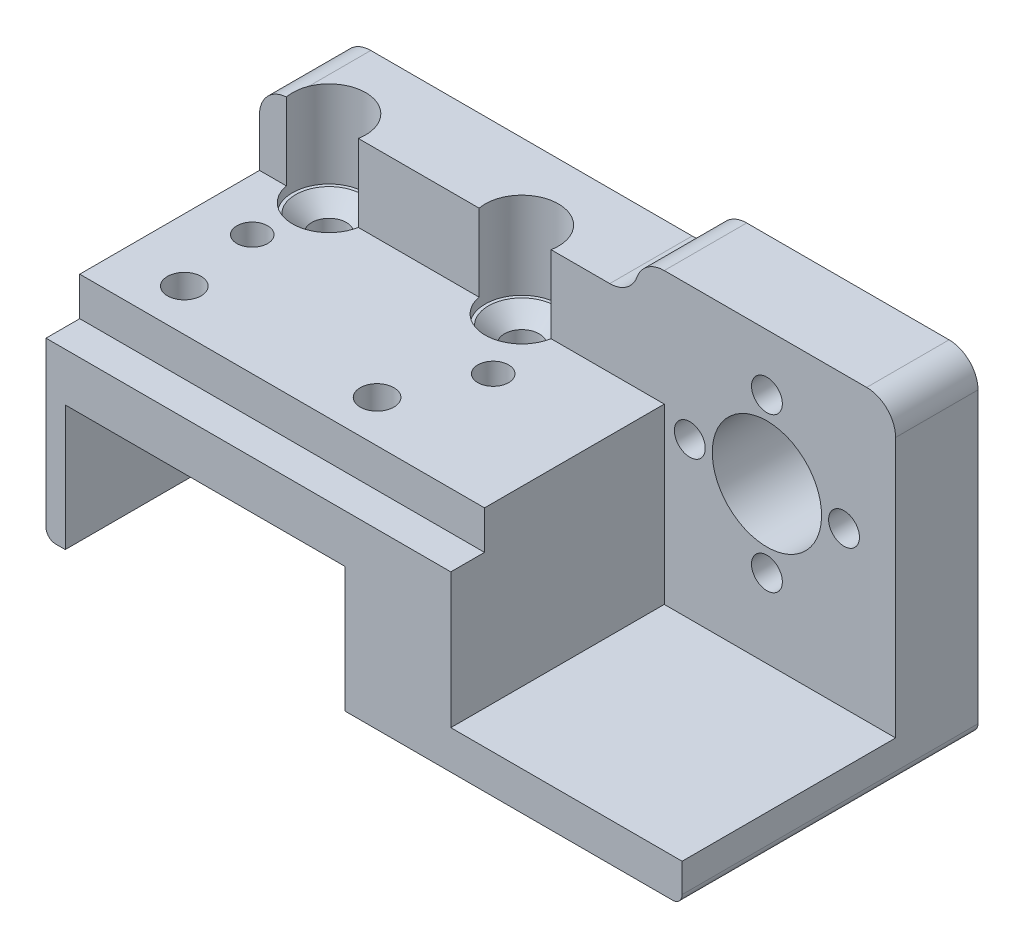
SolidWorks part; units mm, degrees
ref_plane "Front Plane" through (0, 0, 0) normal (0, 0, 1) x (1, 0, 0)
ref_plane "Top Plane" through (0, 0, 0) normal (0, 1, 0) x (1, 0, 0)
ref_plane "Right Plane" through (0, 0, 0) normal (1, 0, 0) x (0, 0, -1)
sketch "Croquis2" plane through (0, 0, 0) normal (0, 0, 1) x (1, 0, 0)
  line L0 (-42.15, -17.65) -> (-49.65, -17.65) construction
  line L1 (-42.15, -17.65) -> (-49.65, -17.65) construction
  line L2 (-49.65, -7.65) -> (-49.65, -17.65) construction
  line L3 (-49.65, -7.65) -> (-49.65, -17.65) construction
  line L5 (-52.65, -20.15) -> (13.35, -20.15)
  line L6 (-52.65, -20.15) -> (-52.65, 13.85)
  line L7 (-52.65, 13.85) -> (13.35, 13.85)
  line L8 (13.35, -20.15) -> (13.35, 13.85)
  line L9 (-50.65, -7.65) -> (-50.65, -7.15)
  line L10 (-21.65, -7.65) -> (-21.65, -17.65)
  line L11 (-21.65, -7.65) -> (-21.65, -20.15)
  line L13 (-50.65, -7.15) -> (-49.65, -7.15)
  line L14 (-21.65, -7.65) -> (-21.65, -7.15)
  line L15 (-21.65, -7.15) -> (-22.65, -7.15)
  line L16 (-50.65, -20.15) -> (-21.65, -20.15)
  line L17 (-30.45, -21.15) -> (-41.85, -21.15) construction
  line L18 (-49.65, -7.15) -> (-22.65, -7.15)
  line L19 (-49.65, -7.15) -> (-22.65, -7.15)
  line L28 (-50.65, -7.65) -> (-50.65, -17.65)
  line L29 (-50.65, -7.65) -> (-50.65, -20.15)
  circle A2 centre (0, 0) radius 5.67
  circle A3 centre (0, 0) radius 5.67
  circle A5 centre (0, 8) radius 1.3
  circle A6 centre (0, 8) radius 1.3
  circle A8 centre (8, 0) radius 1.3
  circle A9 centre (8, 0) radius 1.3
  circle A11 centre (0, -8) radius 1.3
  circle A12 centre (0, -8) radius 1.3
  circle A14 centre (-8, 0) radius 1.3
  circle A15 centre (-8, 0) radius 1.3
  circle M7 centre (0, 8) radius 1.6
  circle M8 centre (0, -8) radius 1.6
  circle M9 centre (8, 0) radius 1.6
  circle M10 centre (-8, 0) radius 1.6
  circle M12 centre (0, 0) radius 10.875
  dimension "D6" = 3
  dimension "D7" = 66
  dimension "D8" = 34
  dimension "D12" = 1
  dimension "D1" = 0.5
  dimension "D2" = 0.3
  dimension "D3" = 0.3
  dimension "D4" = 0.3
  dimension "D5" = 0.3
  dimension "D9" = 0.5
  dimension "D10" = 1
  dimension "D11" = 1
extrude "Saliente-Extruir1" add sketch "Croquis2" along normal offset from surface (30.7 mm away) 2 contours L29 L9 L13 L19 L15 L14 L11 L5 L8 L7 L6 M12 | A3 M12 M8 M10 M9 M7 region at (-20.3724, -1.2856, 0) region at (-10.5674, 0, 0)
sketch "Croquis4" plane through (0, 0, 30.7) normal (0, 0, 1) x (1, 0, 0)
  line L0 (-52.65, 13.85) -> (13.35, 13.85) construction
  line L1 (-10.65, 13.85) -> (13.35, 13.85)
  line L2 (-10.65, 13.85) -> (-10.65, -16.15)
  line L3 (-10.65, -16.15) -> (13.35, -16.15)
  line L4 (13.35, 13.85) -> (13.35, -16.15)
  line L5 (13.35, -20.15) -> (13.35, 13.85) construction
  line M9 (13.35, -20.15) -> (13.35, 13.85)
  line M10 (13.35, 13.85) -> (-52.65, 13.85)
  circle M13 centre (0, 0) radius 5.67
  circle M14 centre (0, -8) radius 1.6
  circle M15 centre (-8, 0) radius 1.6
  circle M16 centre (8, 0) radius 1.6
  circle M17 centre (0, 8) radius 1.6
  dimension "D1" = 24
  dimension "D2" = 30
extrude "Cortar-Extruir2" cut sketch "Croquis4" against normal offset from surface (22.7 mm away) 8 contours L2 L3 M9 M10 M13 M15 M17 M16 M14 region at (1.35, 13.4658, 30.7) up to face at (-27.9, -8.4, 0)
sketch "Croquis6" plane through (0, 0, 30.7) normal (0, 0, 1) x (1, 0, 0)
  line L0 (-30.15, -17.65) -> (-30.15, -13.15) construction
  line L1 (-21.65, -20.15) -> (-50.65, -20.15)
  line L2 (-21.65, -20.15) -> (-21.65, -7.15)
  line L3 (-21.65, -7.15) -> (-50.65, -7.15)
  line L4 (-50.65, -20.15) -> (-50.65, -7.15)
  line L5 (-30.15, -13.15) -> (-42.15, -13.15) construction
  line L6 (-42.15, -13.15) -> (-42.15, -17.65) construction
  line L7 (-29.65, -20.15) -> (-29.65, -12.65)
  line L8 (-29.65, -12.65) -> (-42.65, -12.65)
  line L9 (-42.65, -12.65) -> (-42.65, -20.15)
  line L10 (-29.65, -17.65) -> (-29.65, -12.65) construction
  line L11 (-42.65, -12.65) -> (-42.65, -17.65) construction
  dimension "D1" = 0.5
sketch "Croquis3" plane through (-52.65, 0, 0) normal (-1, 0, 0) x (0, 0, 1)
  line L0 (-2, -7.65) -> (32.7, -7.65) construction
  line L1 (20.85, 1.85) -> (8.55, 1.85)
  line L2 (20.85, 1.85) -> (20.85, 9.85)
  line L3 (20.85, 9.85) -> (8.55, 9.85)
  line L4 (8.55, 1.85) -> (8.55, 9.85)
  line L5 (0, -20.15) -> (0, 13.85) construction
  line L6 (30.7, 13.85) -> (30.7, -20.15) construction
  dimension "D1" = 8
  dimension "D2" = 12.3
  dimension "D3" = 9.5
  dimension "D4" = 9.85
  dimension "D5" = 8.55
extrude "Cortar-Extruir5" cut sketch "Croquis3" against normal blind 42
sketch "Croquis5" plane through (0, 13.85, 0) normal (0, 1, 0) x (1, 0, 0)
  line L0 (-10.65, -20.85) -> (-10.65, -8.55) construction
  line L1 (-52.65, -20.85) -> (-52.65, -8.55) construction
  line L2 (-52.65, -14.7) -> (-11.635, -14.7) construction
  line L5 (-52.65, -20.85) -> (-52.65, -8.55)
  circle A0 centre (-47.25, -14.7) radius 1.6
  circle A1 centre (-22.25, -14.7) radius 1.6
  point P15 (-52.65, -14.7)
  dimension "D3" = 3.2
  dimension "D1" = 11.6
  dimension "D2" = 25
extrude "Cortar-Extruir6" cut sketch "Croquis5" against normal through all contours L2 A0 | A0 L2 | A1 L2 | L2 A1 region at (-47.25, 13.85, 14.0209) region at (-22.25, 13.85, 14.0209) region at (-22.25, 13.85, 15.3791) region at (-47.25, 13.85, 15.3791)
sketch "Croquis7" plane through (0, 13.85, 0) normal (0, 1, 0) x (1, 0, 0)
  line L0 (-52.65, 0) -> (13.35, 0) construction
  line L1 (-52.65, -30.7) -> (-10.65, -30.7)
  line L2 (-52.65, -30.7) -> (-52.65, 0)
  line L3 (-52.65, 0) -> (-10.65, 0)
  line L4 (-10.65, -30.7) -> (-10.65, 0)
  line L5 (-52.65, -8.55) -> (-52.65, -20.85) construction
  line L6 (-52.65, -8.55) -> (-52.65, -20.85)
  line L8 (-52.65, -20.85) -> (-10.65, -20.85)
  line L9 (-52.65, -20.85) -> (-52.65, -30.7)
  line L10 (-52.65, -30.7) -> (-10.65, -30.7)
  line L11 (-10.65, -20.85) -> (-10.65, -30.7)
  line M3 (-10.65, -30.7) -> (-10.65, -8)
  line M6 (13.35, 0) -> (-52.65, 0)
  line M7 (-52.65, 0) -> (-52.65, -30.7)
  line M8 (-52.65, -30.7) -> (-10.65, -30.7)
  circle M15 centre (-47.25, -14.7) radius 1.6
  circle M16 centre (-22.25, -14.7) radius 1.6
extrude "Cortar-Extruir7" cut sketch "Croquis7" against normal up to surface (4 mm away) contours L2 L8 L4 M6 M7 M16 M15 region at (-31.592, 13.85, 10.345) up to face at (-47.25, 9.85, 16.3)
sketch "Croquis9" plane through (-10.65, 0, 0) normal (-1, 0, 0) x (0, 0, 1)
  line L4 (8, 9.85) -> (8, 13.85)
  line L5 (8, 13.85) -> (0, 13.85)
  line L6 (0, 13.85) -> (0, 9.85)
  line L7 (0, 9.85) -> (8, 9.85)
  line L8 (8, 9.85) -> (8, 13.85)
  line L9 (8, 13.85) -> (0, 13.85)
  line L10 (0, 13.85) -> (0, 9.85)
  line L11 (0, 9.85) -> (8, 9.85)
  dimension "D1" = 0
extrude "Saliente-Extruir4" add sketch "Croquis9" along normal blind 3
extrude "Cortar-Extruir8" cut sketch "Croquis7<3>" against normal up to surface (12 mm away) contours L8 M7 M8 M3 region at (-31.65, 13.85, 25.775) up to face at (-47.25, 1.85, 13.1)
sketch "Croquis7<3>" plane through (0, 13.85, 0) normal (0, 1, 0) x (1, 0, 0) same geometry as "Croquis7"
sketch "Croquis11" plane through (0, 1.85, 0) normal (0, 1, 0) x (1, 0, 0)
  line L1 (-47.25, -10.3121) -> (-51.05, -12.5061)
  line L2 (-51.05, -12.5061) -> (-51.05, -16.8939)
  line L3 (-51.05, -16.8939) -> (-47.25, -19.0879)
  line L4 (-47.25, -19.0879) -> (-43.45, -16.8939)
  line L5 (-43.45, -16.8939) -> (-43.45, -12.5061)
  line L6 (-43.45, -12.5061) -> (-47.25, -10.3121)
  line L7 (-22.25, -10.3121) -> (-26.05, -12.5061)
  line L8 (-26.05, -12.5061) -> (-26.05, -16.8939)
  line L9 (-26.05, -16.8939) -> (-22.25, -19.0879)
  line L10 (-22.25, -19.0879) -> (-18.45, -16.8939)
  line L11 (-18.45, -16.8939) -> (-18.45, -12.5061)
  line L12 (-18.45, -12.5061) -> (-22.25, -10.3121)
  circle A0 centre (-46.1299, -7.85) radius 1.5 construction
  circle A1 centre (-26.1299, -7.85) radius 1.5 construction
  circle A2 centre (-26.15, -22.85) radius 1.5 construction
  circle A3 centre (-46.15, -22.85) radius 1.5 construction
  circle A4 centre (-46.1299, -7.85) radius 1.5 construction
  circle A5 centre (-26.1299, -7.85) radius 1.5 construction
  circle A6 centre (-26.15, -22.85) radius 1.5 construction
  circle A7 centre (-46.15, -22.85) radius 1.5 construction
  circle A8 centre (-46.1299, -7.85) radius 3.8
  circle A9 centre (-26.1299, -7.85) radius 3.8
  circle A10 centre (-26.15, -22.85) radius 3.8
  circle A11 centre (-46.15, -22.85) radius 3.8
  circle A12 centre (-47.25, -14.7) radius 3.8 construction
  circle A13 centre (-22.25, -14.7) radius 3.8 construction
  circle A14 centre (-46.1299, -7.85) radius 1.75
  circle A15 centre (-26.1299, -7.85) radius 1.75
  circle A16 centre (-26.15, -22.85) radius 1.75
  circle A17 centre (-46.15, -22.85) radius 1.75
  circle M13 centre (-47.25, -14.7) radius 1.6
  circle M14 centre (-22.25, -14.7) radius 1.6
  line M18 (-10.65, -8.55) -> (-52.65, -8.55)
  dimension "D1" = 7.6
  dimension "D2" = 7.6
  dimension "D3" = 3.5
extrude "Cortar-Extruir9" cut sketch "Croquis11" against normal offset from surface (9 mm away) 1 from surface contours A14 A8 M18 | A14 A8 L1 L6 M18 | L1 A8 L6 | A14 M18 | A14 M18 | A15 A9 M18 | A15 M18 | A15 M18 | A15 A9 M18 region at (-46.8614, 1.85, 11.0938) region at (-46.0098, 1.85, 9.8058) region at (-26.4732, 1.85, 4.1542) region at (-26.1299, 1.85, 9.9873) region at (-46.4732, 1.85, 4.1542) region at (-46.1299, 1.85, 8.9831) region at (-46.1299, 1.85, 7.4676) region at (-26.1299, 1.85, 8.9831) region at (-26.1299, 1.85, 7.4676) up to face at (-47.25, 1.85, 13.1) offset beyond the face yes starting at face at (-25.65, 9.85, 5.5167)
extrude "Cortar-Extruir10" cut sketch "Croquis11<3>" against normal through all contours A14 M18 | A14 M18 | A15 M18 | A15 M18 | A16 | A17 region at (-46.1299, 1.85, 8.9831) region at (-46.1299, 1.85, 7.4676) region at (-26.1299, 1.85, 8.9831) region at (-26.1299, 1.85, 7.4676) region at (-26.15, 1.85, 22.85) region at (-46.15, 1.85, 22.85)
sketch "Croquis11<3>" plane through (0, 1.85, 0) normal (0, 1, 0) x (1, 0, 0) same geometry as "Croquis11"
extrude "Cortar-Extruir11" cut sketch "Croquis11<4>" along normal blind 4 and the other way through all from surface contours A8 L1 L2 L3 L4 L5 L6 M13 | L11 L12 L7 L8 L9 L10 M14 | L1 A8 L6 region at (-46.8614, 1.85, 11.0938) region at (-46.8317, 1.85, 11.6979) region at (-20.408, 1.85, 11.5096) starting at face at (-46.15, -7.15, 24.6)
sketch "Croquis11<4>" plane through (0, 1.85, 0) normal (0, 1, 0) x (1, 0, 0) same geometry as "Croquis11"
hole_wizard "Avellanado para tornillo con cabeza avellanada de clavija hexagonal de M31" positions "Croquis16" profile "Croquis17" countersink size "M3" standard "DIN" end condition through all
sketch "Croquis16" plane through (0, 0.85, 0) normal (0, 1, 0) x (1, 0, 0)
  point P0 (-46.1299, -7.85)
  point P3 (-26.1299, -7.85)
sketch "Croquis17" plane through (-46.1299, 0.85, 7.85) normal (1, 0, 0) x (0, 0, 1)
  line L0 (0, 0) -> (0, 21)
  line L1 (0, 21) -> (1.8, 21)
  line L2 (1.8, 21) -> (1.8, 1.67)
  line L3 (1.8, 1.67) -> (3.47, 0)
  line L5 (3.47, 0) -> (0, 0)
  line L6 (-1.8, 1.67) -> (-3.47, 0) construction
  line L11 (0, -6.35) -> (0, 107.95) construction
  dimension "Diámetro de taladro hasta el siguiente" = 3.6
  dimension "Profundidad de taladro hasta el siguiente" = 21
  dimension "Diámetro de avellanado cercano" = 6.94
  dimension "Ángulo de avellanado cercano" = 90
sketch "Croquis18" plane through (0, 1.85, 0) normal (0, 1, 0) x (1, 0, 0)
  line L0 (-10.65, -8.55) -> (-10.65, -30.7) construction
  line L1 (-52.65, -30.7) -> (-10.65, -30.7)
  line L2 (-52.65, -30.7) -> (-52.65, -27.2)
  line L3 (-52.65, -27.2) -> (-10.65, -27.2)
  line L4 (-10.65, -30.7) -> (-10.65, -27.2)
  dimension "D1" = 3.5
extrude "Cortar-Extruir12" cut sketch "Croquis18" against normal blind 4
sketch "Croquis19" plane through (0, 0, 8) normal (0, 0, 1) x (1, 0, 0)
  line L6 (-10.65, 9.85) -> (-10.65, -16.15)
  line L7 (-10.65, -16.15) -> (13.35, -16.15)
  line L8 (13.35, -16.15) -> (13.35, 13.85)
  line L9 (13.35, 13.85) -> (-13.65, 13.85)
  line L10 (-13.65, 13.85) -> (-13.65, 9.85)
  line L11 (-13.65, 9.85) -> (-10.65, 9.85)
  line L12 (-10.65, 9.85) -> (-10.65, -16.15)
  line L13 (-10.65, -16.15) -> (13.35, -16.15)
  line L14 (13.35, -16.15) -> (13.35, 13.85)
  line L15 (13.35, 13.85) -> (-13.65, 13.85)
  line L16 (-13.65, 13.85) -> (-13.65, 9.85)
  line L17 (-13.65, 9.85) -> (-10.65, 9.85)
  circle A0 centre (0, 0) radius 5.67 construction
  circle A1 centre (0, -8) radius 1.6 construction
  circle A2 centre (8, 0) radius 1.6 construction
  circle A3 centre (0, 8) radius 1.6 construction
  circle A4 centre (-8, 0) radius 1.6 construction
  circle A5 centre (0, 0) radius 5.67
  circle A6 centre (0, -8) radius 1.6
  circle A7 centre (8, 0) radius 1.6
  circle A8 centre (0, 8) radius 1.6
  circle A9 centre (-8, 0) radius 1.6
  dimension "D1" = 0
extrude "Saliente-Extruir5" add sketch "Croquis19" along normal up to surface (0.55 mm away) up to face at (-16.5224, 5.85, 8.55)
fillet "Redondeo1" radius 3 2 edges at (13.35, 13.85, 4.275) (-13.65, 13.85, 4.275)
fillet "Redondeo2" radius 3 1 edges at (-13.65, 9.85, 4.275)
fillet "Redondeo3" radius 3 1 edges at (-52.65, 9.85, 4.275)
fillet "Redondeo4" radius 1 2 edges at (-52.65, -20.15, 15.35) (13.35, -20.15, 15.35)
